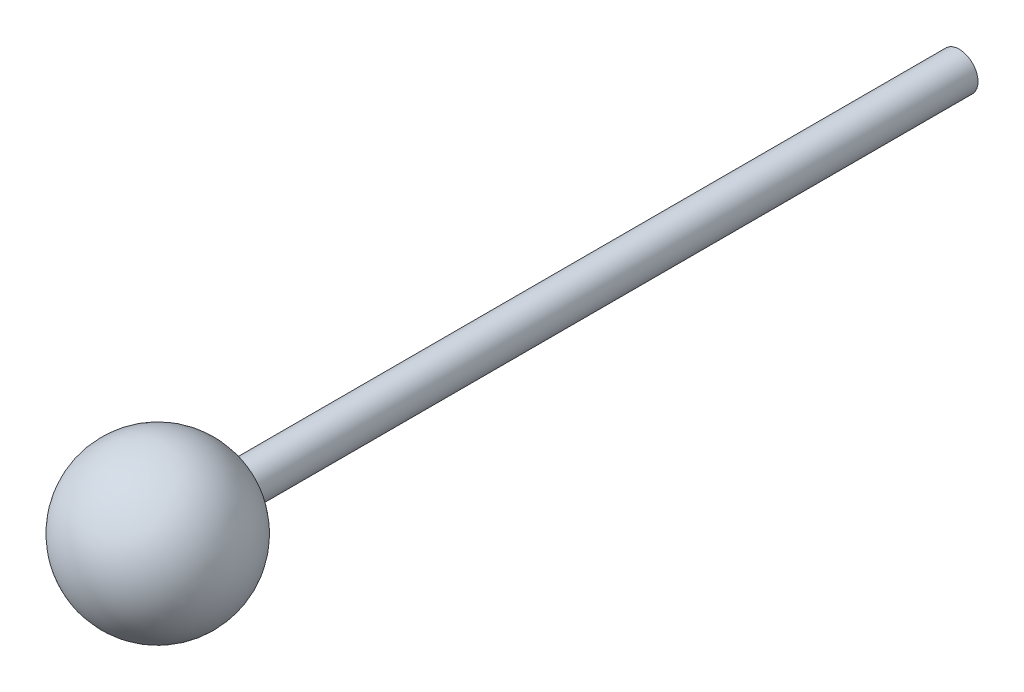
SolidWorks part; units mm, degrees
ref_plane "Front Plane" through (0, 0, 0) normal (0, 0, 1) x (1, 0, 0)
ref_plane "Top Plane" through (0, 0, 0) normal (0, 1, 0) x (1, 0, 0)
ref_plane "Right Plane" through (0, 0, 0) normal (1, 0, 0) x (0, 0, -1)
sketch "Sketch1" plane through (0, 0, 0) normal (0, 0, 1) x (1, 0, 0)
  circle A0 centre (0, 0) radius 0.5938
  dimension "D1" = 1.1875
extrude "Boss-Extrude1" add sketch "Sketch1" along normal blind 25.34
sketch "Sketch2" plane through (0, 0, 25.34) normal (0, 0, 1) x (1, 0, 0)
  line L0 (0, -2.5) -> (0, 2.5)
  arc A0 (0, 2.5) -> (0, -2.5) centre (0, 0) ccw
  point P4 (0, 0)
  dimension "D1" = 5
revolve "Revolve1" add sketch "Sketch2" angle 360 about L0 region at (-1.1094, 0, 25.34)
